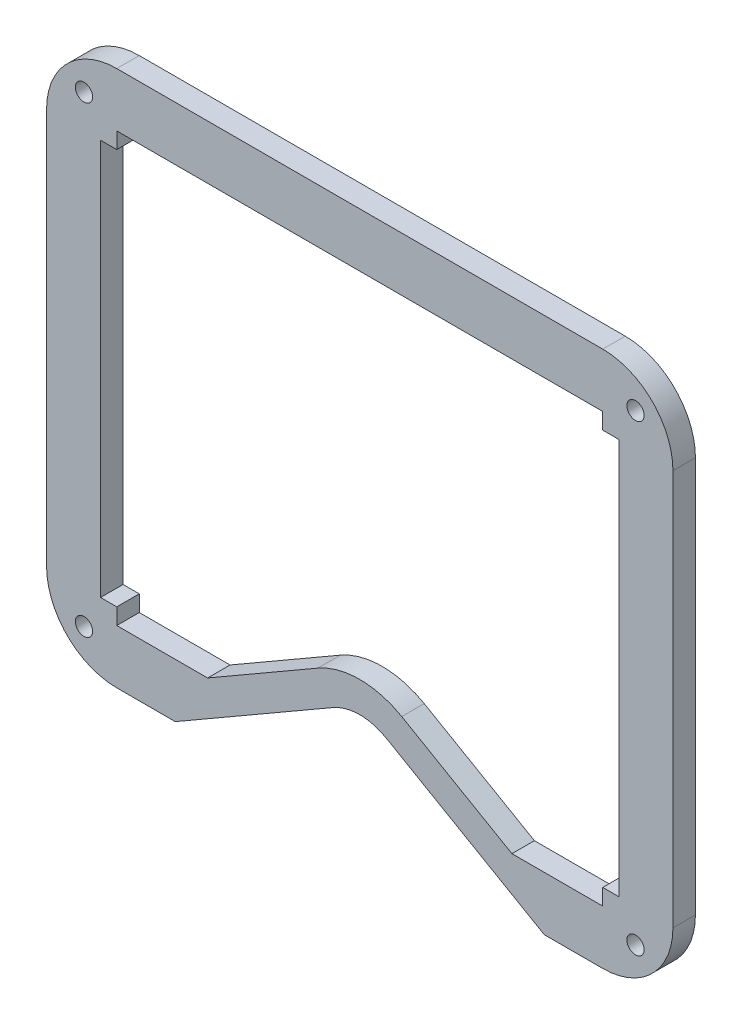
SolidWorks part; units mm, degrees
material "Delrin"
ref_plane "Front Plane" through (0, 0, 0) normal (0, 0, 1) x (1, 0, 0)
ref_plane "Top Plane" through (0, 0, 0) normal (0, 1, 0) x (1, 0, 0)
ref_plane "Right Plane" through (0, 0, 0) normal (1, 0, 0) x (0, 0, -1)
sketch "Sketch1" plane through (0, 0, 0) normal (0, 0, 1) x (1, 0, 0)
  line L0 (-17.145, -18.923) -> (-13.0177, -18.923)
  line L1 (-18.288, 13.97) -> (-18.288, -13.97)
  line L2 (-17.145, -15.113) -> (-10.7365, -15.113)
  line L3 (10.7365, -15.113) -> (17.145, -15.113)
  line L4 (18.288, 13.97) -> (18.288, -13.97)
  line L5 (-1000, 0) -> (49000, 0) construction
  line L6 (26.8751, -22.5509) -> (-27.4868, 23.0642) construction
  line L7 (13.0177, -18.923) -> (17.145, -18.923)
  line L8 (17.145, 15.113) -> (-17.145, 15.113)
  line L9 (-17.145, -18.923) -> (-2.0127, -18.923) construction
  line L10 (-22.098, 13.97) -> (-22.098, -13.97)
  line L11 (1.8796, -12.4924) -> (13.0177, -18.923)
  line L12 (2.0127, -18.923) -> (17.145, -18.923) construction
  line L13 (22.098, 13.97) -> (22.098, -13.97)
  line L14 (17.145, 18.923) -> (-17.145, 18.923)
  line L15 (-17.145, -13.97) -> (-17.145, -15.113)
  line L16 (-18.288, 13.97) -> (-17.145, 13.97)
  line L17 (-18.288, -13.97) -> (-17.145, -13.97)
  line L18 (0, 12.5532) -> (0, -24.2768) construction
  line L19 (17.145, 15.113) -> (17.145, 13.97)
  line L20 (-17.145, 13.97) -> (-17.145, 15.113)
  line L21 (17.145, 13.97) -> (18.288, 13.97)
  line L22 (17.145, -15.113) -> (17.145, -13.97)
  line L23 (17.145, -13.97) -> (18.288, -13.97)
  line L24 (0, -15.748) -> (-1.8796, -12.4924) construction
  line L25 (-1.8796, -12.4924) -> (-13.0177, -18.923)
  line L26 (-2.9591, -10.6227) -> (-10.7365, -15.113)
  line L27 (2.9591, -10.6227) -> (10.7365, -15.113)
  line L28 (-17.145, -15.113) -> (-7.5425, -15.113) construction
  line L29 (-2.9591, -10.6227) -> (-14.0972, -17.0533) construction
  line L30 (7.5425, -15.113) -> (17.145, -15.113) construction
  line L31 (2.9591, -10.6227) -> (14.0972, -17.0533) construction
  arc A0 (1.8796, -12.4924) -> (-1.8796, -12.4924) centre (0, -15.748) ccw
  arc A1 (-17.145, -15.113) -> (-18.288, -13.97) centre (-17.145, -13.97) cw construction
  arc A2 (2.0127, -18.923) -> (-2.0127, -18.923) centre (0, -15.748) ccw construction
  arc A3 (18.288, -13.97) -> (17.145, -15.113) centre (17.145, -13.97) cw construction
  arc A4 (17.145, 15.113) -> (18.288, 13.97) centre (17.145, 13.97) cw construction
  arc A5 (-17.145, -18.923) -> (-22.098, -13.97) centre (-17.145, -13.97) cw
  arc A6 (22.098, -13.97) -> (17.145, -18.923) centre (17.145, -13.97) cw
  arc A7 (17.145, 18.923) -> (22.098, 13.97) centre (17.145, 13.97) cw
  arc A8 (-17.145, 18.923) -> (-22.098, 13.97) centre (-17.145, 13.97) ccw
  circle A9 centre (-19.4575, 16.3268) radius 0.6096
  circle A10 centre (19.4575, 16.3268) radius 0.6096
  arc A11 (-17.145, 15.113) -> (-18.288, 13.97) centre (-17.145, 13.97) ccw construction
  arc A12 (2.9591, -10.6227) -> (-2.9591, -10.6227) centre (0, -15.748) ccw
  circle A13 centre (19.4575, -16.3268) radius 0.6096
  circle A14 centre (-19.4575, -16.3268) radius 0.6096
  arc A18 (7.5425, -15.113) -> (-7.5425, -15.113) centre (0, -15.748) ccw construction
  point P0 (0, 0)
  dimension "D4" = 3.175
  dimension "D6" = 37.846
  dimension "D7" = 44.196
  dimension "D8" = 3.81
  dimension "D9" = 2.159
  dimension "D5" = 1.2192
  dimension "D2" = 4.953
  dimension "D3" = 7.5184
  dimension "D10" = 2.159
  dimension "D12" = 25.4
  dimension "D13" = 40
  dimension "D14" = 30
extrude "Boss-Extrude1" add sketch "Sketch1" along normal blind 1.5875 contours L14 A8 L10 A5 L0 L25 A0 L11 L7 A6 L13 A7 L27 A12 L26 L2 L15 L17 L1 L16 L20 L8 L19 L21 L4 L23 L22 L3 A9 A10 A13 A14 region at (-20.2359, -17.0609, 0)
